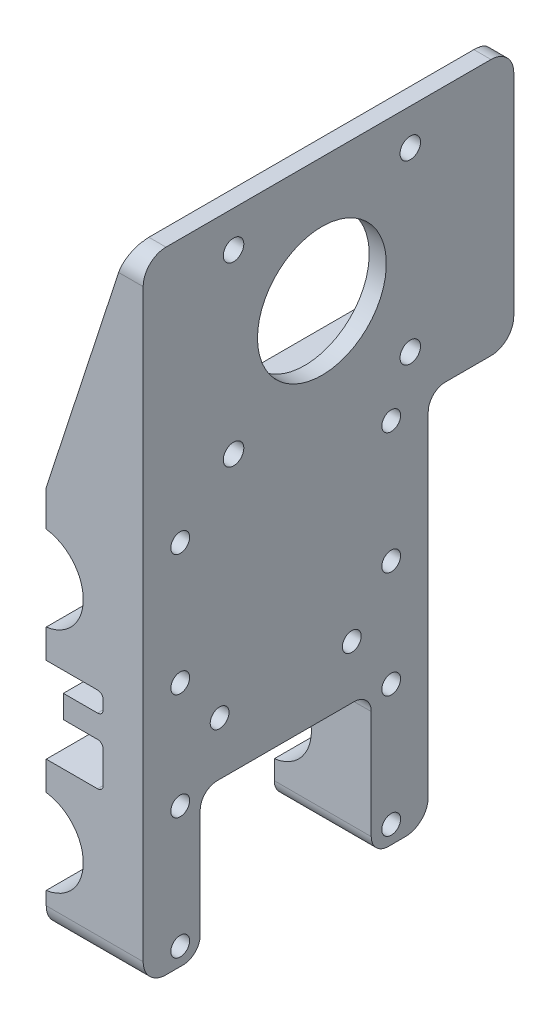
SolidWorks part; units mm, degrees
ref_plane "Front Plane" through (0, 0, 0) normal (0, 0, 1) x (1, 0, 0)
ref_plane "Top Plane" through (0, 0, 0) normal (0, 1, 0) x (1, 0, 0)
ref_plane "Right Plane" through (0, 0, 0) normal (1, 0, 0) x (0, 0, -1)
sketch "Sketch1" plane through (0, 0, 0) normal (0, 0, 1) x (1, 0, 0)
  line L1 (-3.5, -33.77) -> (3.5, -33.77)
  line L2 (-3.5, -33.77) -> (-3.5, 33.77)
  line L3 (-3.5, 33.77) -> (3.5, 33.77)
  line L4 (3.5, -33.77) -> (3.5, 33.77)
  line L5 (-3.5, -33.77) -> (3.5, 33.77) construction
  line L6 (-3.5, 33.77) -> (3.5, -33.77) construction
  point P0 (0, 0)
  dimension "D1" = 67.54
  dimension "D2" = 7
extrude "Boss-Extrude1" add sketch "Sketch1" along normal blind 50
sketch "Sketch2" plane through (-3.5, 0, 0) normal (-1, 0, 0) x (0, 0, 1)
  line L0 (25, 20.635) -> (25, -20.635) construction
  line L1 (0, 33.77) -> (50, 33.77)
  line L2 (0, 33.77) -> (0, 7.5)
  line L3 (0, 7.5) -> (50, 7.5)
  line L4 (50, 33.77) -> (50, 7.5)
  line L5 (0, 33.77) -> (50, 7.5) construction
  line L6 (0, 7.5) -> (50, 33.77) construction
  line L7 (0, -33.77) -> (50, -33.77)
  line L8 (0, -33.77) -> (0, -7.5)
  line L9 (0, -7.5) -> (50, -7.5)
  line L10 (50, -33.77) -> (50, -7.5)
  line L11 (0, -33.77) -> (50, -7.5) construction
  line L12 (0, -7.5) -> (50, -33.77) construction
  line L13 (0, 0) -> (25, 0) construction
  line L14 (0, 33.77) -> (0, -33.77) construction
  line L15 (50, 33.77) -> (50, -33.77) construction
  point P0 (25, 20.635)
  point P5 (25, -20.635)
  dimension "D1" = 15
extrude "Boss-Extrude2" add sketch "Sketch2" along normal blind 10
sketch "Sketch3" plane through (0, 0, 50) normal (0, 0, 1) x (1, 0, 0)
  line L0 (-13.5, 20) -> (-14.5, 20) construction
  line L1 (-13.5, -33.77) -> (-13.5, -7.5) construction
  line L2 (-13.5, -20) -> (-14.5, -20) construction
  line L4 (-14.5, 20) -> (-14.5, -20) construction
  line L5 (-14.5, 0) -> (3.5, 0) construction
  line L6 (3.5, -33.77) -> (3.5, 33.77) construction
  circle A0 centre (-14.5, 20) radius 7.5
  circle A1 centre (-14.5, -20) radius 7.5
  dimension "D1" = 15
  dimension "D2" = 1
  dimension "D3" = 40
extrude "Cut-Extrude1" cut sketch "Sketch3" against normal through all
sketch "Sketch4" plane through (0, -33.77, 0) normal (0, -1, 0) x (1, 0, 0)
  line L0 (13.05, 25) -> (-13.5, 25) construction
  line L1 (-13.5, 0) -> (-13.5, 50) construction
  line L2 (-13.5, 50) -> (3.5, 50) construction
  line L4 (63.05, 40) -> (-36.95, 40)
  line L5 (63.05, 40) -> (63.05, 10)
  line L6 (63.05, 10) -> (-36.95, 10)
  line L7 (-36.95, 40) -> (-36.95, 10)
  line L8 (63.05, 40) -> (-36.95, 10) construction
  line L9 (63.05, 10) -> (-36.95, 40) construction
  point P6 (0, 0)
  circle B0 centre (13.05, 25) radius 8 construction
  circle B1 centre (13.05, 25) radius 14 construction
  dimension "D2" = 25
  dimension "D1" = 26.55
  dimension "D3" = 30
  dimension "D4" = 100
sketch_block_instance "Block2-1"
sketch_block "Block2" parameters "D1"=28
extrude "Cut-Extrude2" cut sketch "Sketch4" against normal blind 25
sketch "Sketch5" plane through (0, 0, 0) normal (0, 0, -1) x (-1, 0, 0)
  line L0 (13.5, 27.433) -> (13.5, 25.9161)
  line L1 (13.5, -12.567) -> (13.5, -14.0839)
  line L2 (13.5, 14.0839) -> (13.5, 12.567)
  line L3 (13.5, -25.9161) -> (13.5, -27.433)
  arc A0 (13.5, 25.9161) -> (13.5, 14.0839) centre (14.5, 20) ccw
  arc A1 (13.5, -14.0839) -> (13.5, -25.9161) centre (14.5, -20) ccw
  arc A2 (13.5, 27.433) -> (13.5, 12.567) centre (14.5, 20) ccw construction
  arc A3 (13.5, 27.433) -> (13.5, 12.567) centre (14.5, 20) ccw
  arc A4 (13.5, -12.567) -> (13.5, -27.433) centre (14.5, -20) ccw construction
  arc A5 (13.5, -12.567) -> (13.5, -27.433) centre (14.5, -20) ccw
  dimension "D1" = 12
extrude "Boss-Extrude3" add sketch "Sketch5" against normal blind 2
sketch "Sketch6" plane through (3.5, 0, 0) normal (1, 0, 0) x (0, 0, -1)
  circle A1 centre (-6.5, 30.652) radius 1.65
  circle A2 centre (-6.5, 30.652) radius 1.65
  circle A3 centre (-6.5, 9.348) radius 1.65
  circle A4 centre (-6.5, 9.348) radius 1.65
  circle A5 centre (-43.5, 9.348) radius 1.65
  circle A6 centre (-43.5, 9.348) radius 1.65
  circle A7 centre (-43.5, 30.652) radius 1.65
  circle A8 centre (-43.5, 30.652) radius 1.65
  circle A9 centre (-43.5, -9.348) radius 1.65
  circle A10 centre (-43.5, -9.348) radius 1.65
  circle A11 centre (-43.5, -30.652) radius 1.65
  circle A12 centre (-43.5, -30.652) radius 1.65
  circle A13 centre (-6.5, -9.348) radius 1.65
  circle A14 centre (-6.5, -9.348) radius 1.65
  circle A15 centre (-6.5, -30.652) radius 1.65
  circle A16 centre (-6.5, -30.652) radius 1.65
  dimension "D1" = 0
  dimension "D2" = 0
  dimension "D3" = 0
  dimension "D4" = 0
  dimension "D5" = 0
  dimension "D6" = 0
  dimension "D7" = 0
  dimension "D8" = 0
extrude "Cut-Extrude3" cut sketch "Sketch6" against normal through all both and the other way through all
sketch "Sketch7" plane through (3.5, 0, 0) normal (1, 0, 0) x (0, 0, -1)
  line L0 (-50, 33.77) -> (15, 33.77)
  line L1 (-50, 33.77) -> (-50, 76.77)
  line L2 (15, 33.77) -> (15, 76.77)
  line L3 (-50, 76.77) -> (15, 76.77)
  point P0 (19.7473, 33.77)
  dimension "D1" = 43
  dimension "D2" = 15
extrude "Boss-Extrude4" add sketch "Sketch7" against normal blind 3
sketch "Sketch8" plane through (3.5, 0, 0) normal (1, 0, 0) x (0, 0, -1)
  line L0 (-18.65, 54.92) -> (-50, 54.92) construction
  line L1 (-50, -33.77) -> (-50, 76.77) construction
  line L2 (15, 76.77) -> (-50, 76.77) construction
  line L3 (-34.15, 70.42) -> (-3.15, 70.42) construction
  circle B0 centre (-3.15, 70.42) radius 1.8
  circle B1 centre (-3.15, 39.42) radius 1.8
  circle B2 centre (-34.15, 70.42) radius 1.8
  circle B3 centre (-18.65, 54.92) radius 11.3
  circle B4 centre (-34.15, 39.42) radius 1.8
  dimension "D1" = 21.85
  dimension "D2" = 31.35
sketch_block_instance "Block1-1"
sketch_block "Block1"
extrude "Cut-Extrude4" cut sketch "Sketch8" against normal through all both and the other way through all
sketch "Sketch11" plane through (3.5, 0, 0) normal (1, 0, 0) x (0, 0, -1)
  line L0 (-36.5908, 0.58) -> (-13.4092, 0.58) construction
  line L2 (-25, 0.58) -> (-25, -8.77) construction
  line L3 (-10, -8.77) -> (-40, -8.77) construction
  line L4 (-40, -8.77) -> (-10, -8.77) construction
  circle A2 centre (-36.5908, 0.58) radius 1.65
  circle A4 centre (-13.4092, 0.58) radius 1.65
  dimension "D2" = 3.3
  dimension "D1" = 9.35
  dimension "D3" = 23.1815
extrude "Cut-Extrude5" cut sketch "Sketch11" against normal through all both and the other way through all
sketch "Sketch12" plane through (-3.5, 0, 0) normal (-1, 0, 0) x (0, 0, 1)
  line L0 (0, 7.5) -> (50, 7.5) construction
  line L1 (0, 0) -> (8, 0)
  line L2 (0, 0) -> (0, 4)
  line L3 (0, 4) -> (8, 4)
  line L4 (8, 0) -> (8, 4)
  line L5 (0, 0) -> (8, 4) construction
  line L6 (0, 4) -> (8, 0) construction
  line L7 (42, 4) -> (50, 4)
  line L8 (42, 4) -> (42, 0)
  line L9 (42, 0) -> (50, 0)
  line L10 (50, 4) -> (50, 0)
  line L11 (42, 4) -> (50, 0) construction
  line L12 (42, 0) -> (50, 4) construction
  line L16 (46, 2) -> (21.8086, 2) construction
  line L17 (50, 7.5) -> (50, -7.5) construction
  line L19 (0, 7.5) -> (0, -7.5) construction
  point P0 (4, 2)
  point P5 (46, 2)
  point P12 (50, 0)
  point P13 (50, 0)
  point P15 (43.6006, 4)
  dimension "D1" = 8
  dimension "D2" = 3.5
  dimension "D3" = 4
extrude "Boss-Extrude6" add sketch "Sketch12" along normal blind 7
sketch "Sketch15" plane through (0, 33.77, 0) normal (0, -1, 0) x (1, 0, 0)
  line L1 (3.5, -15) -> (-13.5, -15)
  line L2 (3.5, -15) -> (3.5, 0)
  line L3 (3.5, 0) -> (-13.5, 0)
  line L4 (-13.5, -15) -> (-13.5, 0)
extrude "Boss-Extrude7" add sketch "Sketch15" along normal blind 2
fillet "Fillet4" radius 3 1 edges at (-5, 31.77, 0)
fillet "Fillet5" radius 3 4 edges at (-5, -33.77, 40) (-5, -33.77, 10) (-5, -8.77, 10) (-5, -8.77, 40)
fillet "Fillet6" radius 1 8 edges at (-3.5, 2, 8) (-3.5, 2, 42) (-3.5, 0, 46) (-3.5, 4, 46) (-3.5, 4, 4) (-3.5, 0, 4) (-3.5, -7.5, 25)
sketch "Sketch17" plane through (0, 0, 50) normal (0, 0, 1) x (1, 0, 0)
  line L0 (0.5, 76.77) -> (-13.5, 33.77)
  line L1 (-13.5, 33.77) -> (0.5, 33.77)
  line L2 (0.5, 33.77) -> (0.5, 76.77)
extrude "Boss-Extrude8" add sketch "Sketch17" against normal blind 3
sketch "Sketch18" plane through (0, 0, -15) normal (0, 0, -1) x (-1, 0, 0)
  line L0 (-0.5, 76.77) -> (13.5, 33.77)
  line L1 (13.5, 33.77) -> (-0.5, 33.77)
  line L2 (-0.5, 33.77) -> (-0.5, 76.77)
extrude "Boss-Extrude9" add sketch "Sketch18" against normal blind 3
fillet "Fillet7" radius 4 5 edges at (-5, -33.77, 50) (-5, -33.77, 0) (-5, 31.77, -15) (2, 76.77, -15) (2, 76.77, 50)
sketch "Sketch19" plane through (-3.5, 0, 0) normal (-1, 0, 0) x (0, 0, 1)
  line L1 (13.4092, 3.8709) -> (10.5592, 2.2254)
  line L2 (10.5592, 2.2254) -> (10.5592, -1.0654)
  line L3 (10.5592, -1.0654) -> (13.4092, -2.7109)
  line L4 (13.4092, -2.7109) -> (16.2592, -1.0654)
  line L5 (16.2592, -1.0654) -> (16.2592, 2.2254)
  line L6 (16.2592, 2.2254) -> (13.4092, 3.8709)
  line L7 (36.5908, 3.8709) -> (33.7408, 2.2254)
  line L8 (33.7408, 2.2254) -> (33.7408, -1.0654)
  line L9 (33.7408, -1.0654) -> (36.5908, -2.7109)
  line L10 (36.5908, -2.7109) -> (39.4408, -1.0654)
  line L11 (39.4408, -1.0654) -> (39.4408, 2.2254)
  line L12 (39.4408, 2.2254) -> (36.5908, 3.8709)
  circle A0 centre (13.4092, 0.58) radius 2.85 construction
  circle A1 centre (36.5908, 0.58) radius 2.85 construction
  dimension "D1" = 5.7
extrude "Cut-Extrude7" cut sketch "Sketch19" against normal blind 2.5
